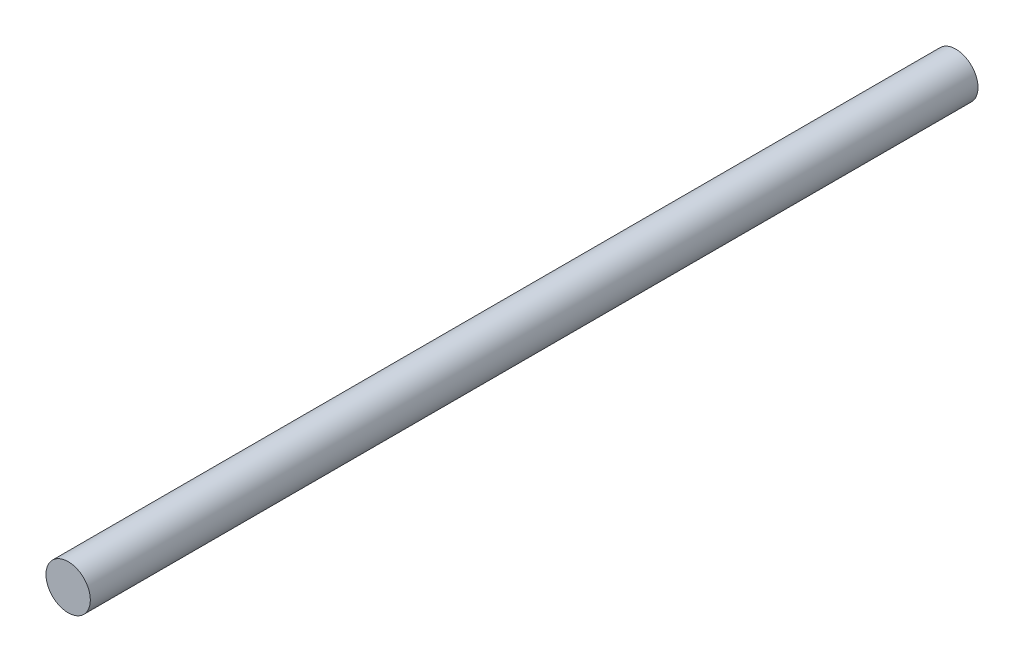
SolidWorks part; units mm, degrees
ref_plane "正面" through (0, 0, 0) normal (0, 0, 1) x (1, 0, 0)
ref_plane "平面" through (0, 0, 0) normal (0, 1, 0) x (1, 0, 0)
ref_plane "右側面" through (0, 0, 0) normal (1, 0, 0) x (0, 0, -1)
sketch "ｽｹｯﾁ1" plane through (0, 0, 0) normal (0, 0, 1) x (1, 0, 0)
  circle A0 centre (0, 0) radius 0.25
  dimension "D1" = 0.5
extrude "ﾎﾞｽ - 押し出し1" add sketch "ｽｹｯﾁ1" along normal blind 10 contours A0
equation "\"cylinder_diameter\"= 0.5"
equation "\"common_variable\" = 2"
equation "\"D1@ｽｹｯﾁ1\"= \"cylinder_diameter\""
